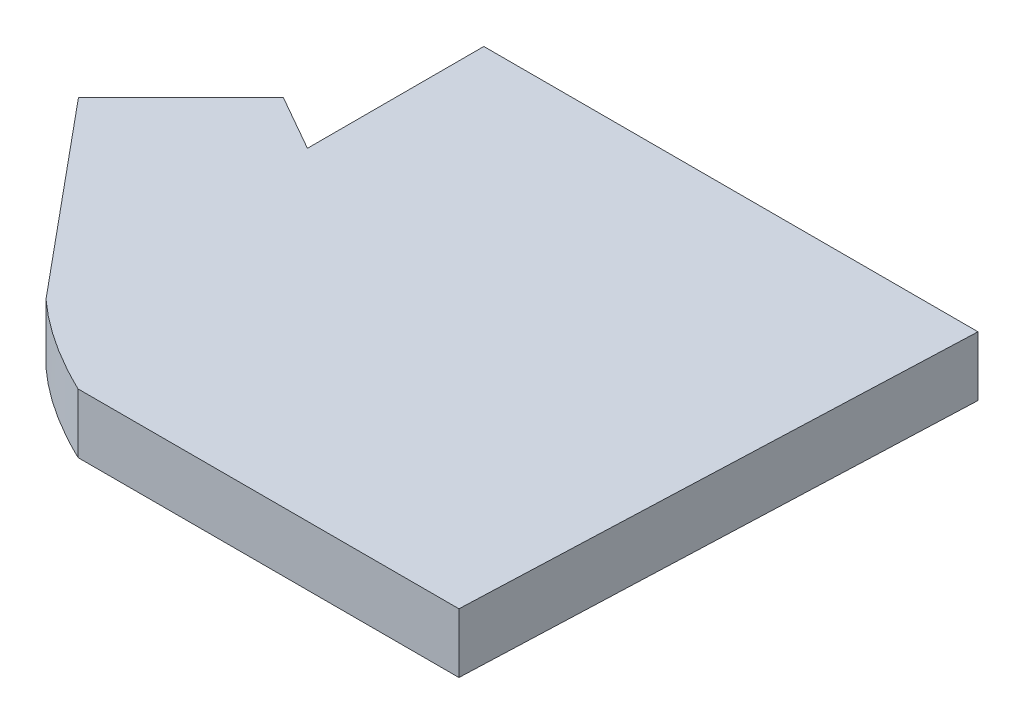
SolidWorks part; units mm, degrees
ref_plane "Front Plane" through (0, 0, 0) normal (0, 0, 1) x (1, 0, 0)
ref_plane "Top Plane" through (0, 0, 0) normal (0, 1, 0) x (1, 0, 0)
ref_plane "Right Plane" through (0, 0, 0) normal (1, 0, 0) x (0, 0, -1)
sketch "Sketch1" plane through (0, 0, 0) normal (0, 1, 0) x (1, 0, 0)
  line L0 (-13.9285, -6.6) -> (69.0715, -6.6)
  line L1 (69.0715, -6.6) -> (65.7758, -90.4854)
  line L3 (65.7758, -90.4854) -> (1.8057, -90.4854)
  line L4 (-13.9285, -6.6) -> (-13.9285, -36.2299)
  line L5 (-40.5595, -48.0529) -> (-13.9285, -80.1379)
  line L6 (-23.3594, -30.8528) -> (-40.5595, -48.0529)
  line L7 (-13.9285, -36.2299) -> (-23.3594, -30.8528)
  line L8 (-40.932, -53.332) -> (-24.668, -37.068) construction
  line L12 (4.1, -4.6) -> (-4.1, -4.6) construction
  spline S1 degree 2 poles (-13.9285, -80.1379) (-7.5226, -85.9916) (1.8057, -90.4854) knots 0 0 0 1 1 1
  dimension "D1" = 83
  dimension "D2" = 2
extrude "Boss-Extrude1" add sketch "Sketch1" along normal blind 5 and the other way blind 5
sketch "Sketch2" plane through (0, 0, 0) normal (0, 1, 0) x (1, 0, 0)
  line L0 (-9.37, 7.52) -> (73.63, 7.52) construction
  line L1 (73.63, 7.52) -> (77.0859, -26.1853) construction
  line L2 (77.0859, -26.1853) -> (60, -92.48) construction
  line L3 (60, -92.48) -> (0, -92.48) construction
  line L4 (0, -92.48) -> (-13.3522, -26.1853) construction
  line L5 (-13.3522, -26.1853) -> (-9.37, 7.52) construction
  line L6 (0, -92.48) -> (0, 7.52) construction
  line L7 (0, -92.48) -> (-39.3219, -55.4519) construction
  line L8 (-39.3219, -55.4519) -> (-24.668, -37.068) construction
  line L9 (-24.668, -37.068) -> (-13.3522, -26.1853) construction
  line L10 (21.42, 7.52) -> (21.42, -92.48) construction
  line L11 (42.84, 7.52) -> (42.84, -92.48) construction
  line L12 (64.26, 7.52) -> (64.26, -75.9509) construction
  line L13 (76.0042, -15.6353) -> (-12.1057, -15.6353) construction
  line L14 (-8.5728, -49.9154) -> (70.97, -49.9154) construction
  line L15 (-9.37, 7.52) -> (9.37, 7.52)
  line L16 (73.63, 7.52) -> (54.89, 7.52)
  line L17 (54.89, 7.52) -> (64.26, 7.52)
  line L18 (33.47, 7.52) -> (52.21, 7.52)
  line L19 (12.05, 7.52) -> (30.79, 7.52)
  spline S0 degree 3 poles (-24.668, -37.068) (-25.0537, -36.7059) (-25.7619, -36.0411) (-26.7353, -35.1295) (-28.0424, -33.9071) (-29.2031, -32.8245) (-30.7142, -31.418) (-32.1196, -30.112) (-34.552, -27.8566) (-36.7318, -25.839) (-39.4542, -23.3171) (-41.6352, -21.2933) (-44.115, -18.9831) (-45.906, -17.309) (-47.5157, -15.8001) (-48.9606, -14.444) (-50.2857, -13.2006) (-51.3935, -12.1603) (-52.3511, -11.2593) (-53.3729, -10.2955) (-54.4927, -9.2355) (-55.8015, -7.9921) (-56.6965, -7.137) (-57.2305, -6.6269) knots 0 0 0 0 0.035582 0.065325 0.089678 0.15593 0.172056 0.228511 0.284969 0.395211 0.428397 0.534723 0.595442 0.656419 0.699627 0.743832 0.789646 0.821914 0.846336 0.87839 0.916737 0.950329 1 1 1 1 construction
  point P21 (0, 7.52)
  point P22 (76.9215, -31.775)
  point P28 (42.84, 7.52)
  point P31 (21.42, 7.52)
  point P32 (72.8535, -26.1853)
  point P33 (0, 0)
  point P34 (0, 0)
  point P35 (0, 0)
  point P37 (0, -92.48)
  point P38 (0, 0)
  point P39 (0, 0)
  point P40 (-35.7468, -57.0567)
  point P41 (-19.3355, -28.857)
  point P42 (-21.1894, -40.1894)
  point P45 (0, 0)
  point P46 (-39.3219, -55.4519)
  dimension "D1" = 83
  dimension "D2" = 100
  dimension "D3" = 60
  dimension "D4" = 18.74
  dimension "D5" = 18.74
  dimension "D6" = 10.55
  dimension "D7" = 18.74
  dimension "D8" = 18.74
  dimension "D9" = 2.68
  dimension "D10" = 2.68
ref_plane "Plane1" through (0, 0, -7.52) normal (0, 0, 1) x (1, 0, 0)
ref_plane "Plane2" through (0, 0, 92.48) normal (0, 0, -1) x (-1, 0, 0)
ref_plane "Plane jari tengah" through (21.42, 0, 0) normal (-1, 0, 0) x (0, 0, 1)
ref_plane "Plane telunjuk" through (0, 0, 0) normal (1, 0, 0) x (0, 0, -1)
ref_plane "Plane Jari MANIS" through (42.84, 0, 0) normal (-1, 0, 0) x (0, 0, 1)
ref_plane "Plane KELINGKING" through (64.26, 0, 0) normal (-1, 0, 0) x (0, 0, 1)
sketch "Sketch8" plane through (0, 0, 92.48) normal (0, 0, -1) x (-1, 0, 0)
  line L0 (-60, 0) -> (0, 0) construction
  ellipse E0 centre (-30, 0) end of major axis (-60, 0) minor radius 14
  point P1 (0, 0)
  point P9 (-30, 0)
  point P10 (0, 0)
  point P11 (0, 0)
  point P13 (-30.6311, 13.6523)
  dimension "D1" = 28
sketch "Sketch3" plane through (21.42, 0, 0) normal (-1, 0, 0) x (0, 0, 1)
  line L0 (-7.52, 9.9745) -> (0.9825, 14.5812) construction
  line L1 (0.9825, 14.5812) -> (92.48, 14.5812) construction
  line L2 (92.48, 14.5812) -> (92.48, -18.4188) construction
  line L3 (92.48, -18.4188) -> (-7.52, -18.4188) construction
  line L4 (-7.52, -18.4188) -> (-7.52, 9.9745) construction
  line L5 (25.1136, 0) -> (25.1136, 14.5812) construction
  line L6 (-7.52, 0) -> (92.48, 0) construction
  line L7 (25.1136, 0) -> (25.1136, -18.4188) construction
  line L8 (11.0531, -18.4188) -> (26.0531, -18.4188)
  line L9 (13.6136, 14.5812) -> (36.6136, 14.5812) construction
  point P3 (18.5683, -17.0437)
  point P8 (0, 0)
  point P16 (0, 0)
  point P21 (18.5531, -18.4188)
  point P23 (25.1136, 14.5812)
  dimension "D1" = 33
  dimension "D2" = 23
  dimension "D3" = 15
sketch "Sketch T tengah" plane through (21.42, 0, 0) normal (-1, 0, 0) x (0, 0, 1)
  line L1 (-7.52, -18.4188) -> (-7.52, 9.9745) construction
  line L3 (-7.72, -8.3628) -> (0.6719, -4.4495) construction
  spline S0 degree 1 poles (36.6136, 14.5812) (92.48, 13.4152) knots 0 0 1 1
  spline S1 degree 3 poles (11.0531, -18.4188) (2.4609, -15.2512) (-3.6722, -11.7151) (-7.52, -8.2695) knots 0 0 0 0 1 1 1 1
  spline S2 degree 3 poles (26.0531, -18.4188) (48.2241, -13.6357) (72.4199, -31.5211) (92.48, -13.4152) knots 0 0 0 0 1 1 1 1
  spline S3 degree 2 poles (13.6136, 14.5812) (4.6225, 13.6335) (-7.52, 5.7198) knots 0 0 0 1 1 1
  spline S4 degree 2 poles (11.0531, -18.4188) (19.1677, -19.901) (26.9681, -18.2343) knots 0 0 0 1 1 1
  spline S5 degree 2 poles (13.6136, 14.5812) (25.6603, 14.8212) (37.7018, 14.5585) knots 0 0 0 1 1 1
  point P10 (0, 0)
  point P11 (0, 0)
  point P19 (70.2971, -21.7138)
sketch "Sketch T Telunjuk" plane through (0, 0, 0) normal (1, 0, 0) x (0, 0, -1)
  line L0 (-92.48, 14.5812) -> (-92.48, -18.4188) construction
  line L1 (-92.48, -18.4188) -> (7.52, -18.4188) construction
  line L2 (7.52, -18.4188) -> (7.52, 9.9745) construction
  line L3 (-0.9825, 14.5812) -> (-92.48, 14.5812) construction
  line L4 (7.52, 9.9745) -> (-0.9825, 14.5812) construction
  line L5 (-11.0531, -18.4188) -> (-26.0531, -18.4188) construction
  line L6 (-25.1136, 0) -> (-25.1136, -18.4188) construction
  line L7 (-13.6136, 14.5812) -> (-36.6136, 14.5812) construction
  line L8 (-25.1136, 0) -> (-25.1136, 14.5812) construction
  line L9 (-92.48, 14.5812) -> (-92.48, -18.4188) construction
  line L10 (-92.48, -18.4188) -> (7.52, -18.4188) construction
  line L11 (7.52, -18.4188) -> (7.52, 9.9745) construction
  line L12 (-0.9825, 14.5812) -> (-92.48, 14.5812) construction
  line L13 (7.52, 9.9745) -> (-0.9825, 14.5812) construction
  line L14 (-11.0531, -18.4188) -> (-26.0531, -18.4188)
  line L15 (-25.1136, 0) -> (-25.1136, -18.4188) construction
  line L16 (-13.6136, 14.5812) -> (-36.6136, 14.5812)
  line L17 (-25.1136, 0) -> (-25.1136, 14.5812) construction
  line L22 (-92.48, 2.3377) -> (-92.48, -9.5106) construction
  spline S0 degree 2 poles (-13.6136, 14.5812) (-1.5806, 12.0378) (7.52, 4.7617) knots 0 0 0 1 1 1
  spline S1 degree 3 poles (-36.6136, 14.5812) (-55.7606, 12.6324) (-92.48, 8.8052) (-92.48, 0) knots 0 0 0 0 1 1 1 1
  spline S2 degree 2 poles (7.52, -9.651) (-0.9831, -15.409) (-11.0531, -18.4188) knots 0 0 0 1 1 1
  spline S3 degree 3 poles (-26.0531, -18.4188) (-34.8378, -16.2128) (-50.4913, -20.7443) (-75.8395, -26.8447) (-92.48, -20.3045) (-92.48, 0) knots 0 0 0 0 0.475651 0.575651 1 1 1 1
  spline S4 degree 2 poles (-11.0531, -18.4188) (-19.9341, -19.7801) (-28.5243, -17.9627) knots 0 0 0 1 1 1
  spline S5 degree 2 poles (-36.6136, 14.5812) (-22.7731, 17.3571) (-9.731, 13.6155) knots 0 0 0 1 1 1
  point P14 (0, 0)
  point P16 (0, 0)
  point P20 (-81.8451, -18.4188)
  point P23 (0, 0)
  point P27 (0, 0)
  point P28 (-57.3341, -20.0098)
  point P30 (-64.5022, -21.2181)
  point P31 (0, 0)
  point P32 (-67.198, -23.5654)
  point P33 (-64.047, -23.9476)
sketch "Sketch T manis" plane through (42.84, 0, 0) normal (-1, 0, 0) x (0, 0, 1)
  line L0 (13.6136, 14.5812) -> (36.6136, 14.5812) construction
  line L1 (11.0531, -18.4188) -> (26.0531, -18.4188) construction
  line L2 (-7.52, 9.9745) -> (0.9825, 14.5812) construction
  line L3 (25.1136, 0) -> (25.1136, -18.4188) construction
  line L4 (25.1136, 0) -> (25.1136, 14.5812) construction
  line L5 (-7.52, -18.4188) -> (-7.52, 9.9745) construction
  line L6 (92.48, -18.4188) -> (-7.52, -18.4188) construction
  line L7 (92.48, 14.5812) -> (92.48, -18.4188) construction
  line L8 (0.9825, 14.5812) -> (92.48, 14.5812) construction
  line L9 (13.6136, 14.5812) -> (36.6136, 14.5812) construction
  line L10 (11.0531, -18.4188) -> (26.0531, -18.4188)
  line L11 (-7.52, 9.9745) -> (0.9825, 14.5812) construction
  line L12 (25.1136, 0) -> (25.1136, -18.4188)
  line L13 (25.1136, 0) -> (25.1136, 14.5812)
  line L14 (-7.52, -18.4188) -> (-7.52, 9.9745) construction
  line L15 (92.48, -18.4188) -> (-7.52, -18.4188) construction
  line L16 (92.48, 14.5812) -> (92.48, -18.4188) construction
  line L17 (0.9825, 14.5812) -> (92.48, 14.5812) construction
  line L18 (30.3671, 14.6142) -> (43.0115, 14.5474) construction
  spline S0 degree 2 poles (-7.52, -12.0108) (1.4272, -16.457) (11.0531, -18.4188) knots 0 0 0 1 1 1
  spline S1 degree 1 poles (11.0531, -18.4188) (26.0531, -18.4188) knots 0 0 1 1
  spline S2 degree 1 poles (11.0531, -18.4188) (26.0531, -18.4188) knots 0 0 1 1
  spline S3 degree 2 poles (-7.52, 5.7198) (2.2712, 12.9568) (13.6136, 14.5812) knots 0 0 0 1 1 1
  spline S4 degree 3 poles (36.6136, 14.5812) (55.2526, 14.4826) (73.8747, 13.6038) (92.48, 12.6529) knots 0 0 0 0 1 1 1 1
  spline S5 degree 3 poles (26.0531, -18.4188) (38.0342, -16.503) (58.9199, -17.2354) (83.2571, -25.1075) (92.48, -12.6529) knots 0 0 0 0 0.473056 1 1 1 1
  spline S6 degree 3 poles (26.0531, -18.4188) (48.2241, -13.6357) (72.4199, -31.5211) (92.48, -13.4152) knots 0 0 0 0 1 1 1 1 construction
  spline S7 degree 2 poles (11.0531, -18.4188) (19.948, -19.5169) (28.6529, -18.034) knots 0 0 0 1 1 1
  spline S8 degree 3 poles (36.6136, 14.5812) (28.6207, 14.6235) (16.536, 16.1755) (7.5843, 13.2899) knots 0 0 0 0 1 1 1 1
sketch "Sketch T kelingking" plane through (64.26, 0, 0) normal (-1, 0, 0) x (0, 0, 1)
  line L0 (13.6136, 14.5812) -> (36.6136, 14.5812) construction
  line L1 (11.0531, -18.4188) -> (26.0531, -18.4188) construction
  line L2 (-7.52, 9.9745) -> (0.9825, 14.5812) construction
  line L3 (-7.52, -18.4188) -> (-7.52, 9.9745) construction
  line L4 (92.48, -18.4188) -> (-7.52, -18.4188) construction
  line L5 (92.48, 14.5812) -> (92.48, -18.4188) construction
  line L6 (0.9825, 14.5812) -> (92.48, 14.5812) construction
  line L7 (13.6136, 14.5812) -> (36.6136, 14.5812) construction
  line L8 (11.0531, -18.4188) -> (26.0531, -18.4188) construction
  line L9 (-7.52, 9.9745) -> (0.9825, 14.5812) construction
  line L10 (-7.52, -18.4188) -> (-7.52, 9.9745) construction
  line L11 (92.48, -18.4188) -> (-7.52, -18.4188) construction
  line L12 (92.48, 14.5812) -> (92.48, -18.4188) construction
  line L13 (0.9825, 14.5812) -> (92.48, 14.5812) construction
  line L18 (75.9509, 7.4976) -> (75.9509, -25.1077) construction
  spline S0 degree 3 poles (36.6136, 14.5812) (73.4975, 8.4898) (75.9509, 6.4971) (75.9509, 0) knots 0 0 0 0 1 1 1 1
  spline S1 degree 3 poles (26.0531, -18.4188) (63.7188, -17.6108) (75.9509, -7.3136) (75.9509, 0) knots 0 0 0 0 1 1 1 1
  spline S2 degree 2 poles (13.6136, 14.5812) (2.4977, 12.7323) (-7.52, 6.7519) knots 0 0 0 1 1 1
  spline S3 degree 2 poles (11.0531, -18.4188) (1.1233, -16.9603) (-7.52, -10.806) knots 0 0 0 1 1 1
  spline S5 degree 2 poles (26.0531, -18.4188) (16.4443, -19.8612) (7.1891, -17.6615) knots 0 0 0 1 1 1
  spline S6 degree 3 poles (36.6136, 14.5812) (27.5043, 16.0856) (18.5693, 15.8318) (9.8085, 13.8198) knots 0 0 0 0 1 1 1 1
  point P12 (87.594, -4.0111)
  point P14 (68.3465, -3.5592)
  point P15 (0, 0)
  point P17 (59.4344, -17.6615)
  point P20 (51.2627, -15.6378)
  point P22 (0, 0)
  point P24 (69.6728, -3.3805)
ref_plane "Plane7" through (-39, 0, 39) normal (0.7071, 0, -0.7071) x (-0.7071, 0, -0.7071)
sketch "Sketch9" plane through (-39, 0, 39) normal (0.7071, 0, -0.7071) x (-0.7071, 0, -0.7071)
  line L0 (-59.4378, 0) -> (-11.7954, -17.3404)
  line L1 (-59.4378, 0) -> (-36.4348, 0) construction
  line L2 (-11.7954, -17.3404) -> (-7.097, -19.0505) construction
  point P2 (0, 0)
  dimension "D3" = 5
  dimension "D1" = 20
  dimension "D2" = 50.7
ref_plane "Plane9" through (4.9164, -19.103, 4.9164) normal (-0.2418, 0.9397, -0.2418) x (-0.6645, -0.342, -0.6645)
ref_plane "Plane10" through (-39, 0, 39) normal (0.7071, 0, -0.7071) x (-0.6645, -0.342, -0.6645)
sketch "Sketch11" plane through (-39, 0, 39) normal (0.7071, 0, -0.7071) x (-0.6645, -0.342, -0.6645)
  line L0 (-0.1533, 0.2386) -> (-0.1533, -40.8965) construction
  point P4 (-0.1533, -20.3289)
sketch "Sketch10" plane through (4.9164, -19.103, 4.9164) normal (-0.2418, 0.9397, -0.2418) x (-0.6645, -0.342, -0.6645)
  circle A0 centre (-5.1533, 55.1543) radius 5
sketch "Sketch12" plane through (4.9164, -19.103, 4.9164) normal (-0.2418, 0.9397, -0.2418) x (-0.6645, -0.342, -0.6645)
  line L0 (-0.1533, 45.9842) -> (-0.1533, 64.3244) construction
  point P4 (-0.1533, 55.1543)
ref_plane "Plane12" through (0.1019, 0.0524, 0.1019) normal (0.6645, 0.342, 0.6645) x (0.7473, -0.3041, -0.5908)
